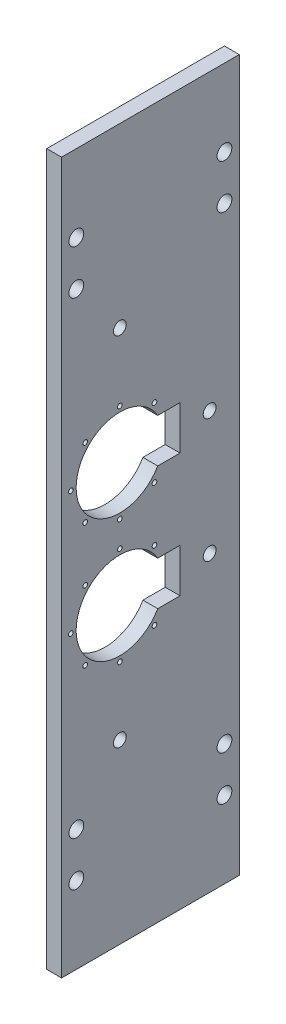
SolidWorks part; units mm, degrees
material "1060 Alloy"
ref_plane "Front Plane" through (0, 0, 0) normal (1, 0, 0) x (0, 1, 0)
ref_plane "Top Plane" through (0, 0, 0) normal (0, 0, 1) x (0, 1, 0)
ref_plane "Right Plane" through (0, 0, 0) normal (0, 1, 0) x (-1, 0, 0)
sketch "Sketch1" plane through (0, 0, 0) normal (1, 0, 0) x (0, 1, 0)
  line L0 (0, 76.2) -> (0, -76.2) construction
  line L1 (-304.8, 76.2) -> (304.8, 76.2)
  line L2 (-304.8, 76.2) -> (-304.8, -76.2)
  line L3 (-304.8, -76.2) -> (304.8, -76.2)
  line L4 (304.8, 76.2) -> (304.8, -76.2)
  line L5 (-304.8, 76.2) -> (304.8, -76.2) construction
  line L6 (-304.8, -76.2) -> (304.8, 76.2) construction
  line L7 (53, 26.2) -> (53, -11.3) construction
  line L8 (53, 26.2) -> (71.75, -6.276) construction
  line L9 (34.25, -6.276) -> (34.25, -25.4)
  line L10 (34.25, -25.4) -> (71.75, -25.4)
  line L11 (71.75, -25.4) -> (71.75, -6.276)
  line L12 (-304.8, 0) -> (304.8, 0) construction
  line L13 (-34.25, -25.4) -> (-71.75, -25.4)
  line L14 (-34.25, -6.276) -> (-34.25, -25.4)
  line L15 (-71.75, -25.4) -> (-71.75, -6.276)
  arc A0 (71.75, -6.276) -> (34.25, -6.276) centre (53, 26.2) ccw
  circle A1 centre (53, 26.2) radius 42 construction
  circle A2 centre (53, 68.2) radius 2
  circle A3 centre (82.6985, 55.8985) radius 2
  circle A4 centre (95, 26.2) radius 2
  circle A5 centre (82.6985, -3.4985) radius 2
  circle A6 centre (53, -15.8) radius 2 [skipped]
  circle A7 centre (23.3015, -3.4985) radius 2
  circle A8 centre (11, 26.2) radius 2
  circle A9 centre (23.3015, 55.8985) radius 2
  circle A10 centre (238.76, 63.5) radius 6.35
  circle A11 centre (200.66, 63.5) radius 6.35
  circle A12 centre (200.66, -63.5) radius 6.35
  circle A13 centre (238.76, -63.5) radius 6.35
  circle A14 centre (-200.66, 63.5) radius 6.35
  circle A15 centre (-238.76, 63.5) radius 6.35
  circle A16 centre (-238.76, -63.5) radius 6.35
  circle A17 centre (-200.66, -63.5) radius 6.35
  circle A18 centre (-82.6985, -3.4985) radius 2
  circle A19 centre (-95, 26.2) radius 2
  circle A20 centre (-82.6985, 55.8985) radius 2
  circle A21 centre (-53, 68.2) radius 2
  circle A22 centre (-23.3015, 55.8985) radius 2
  circle A23 centre (-11, 26.2) radius 2
  circle A24 centre (-23.3015, -3.4985) radius 2
  arc A25 (-71.75, -6.276) -> (-34.25, -6.276) centre (-53, 26.2) cw
  point P0 (0, 0)
  point P8 (53, 26.2)
  point P18 (53, -50.8)
  point P19 (153, 26.2)
  point P71 (-153, 26.2)
  point P72 (-53, -50.8)
  dimension "D9" = 84
  dimension "D10" = 4
  dimension "D14" = 12.7
  dimension "D17" = 12.7
  dimension "D1" = 152.4
  dimension "D2" = 609.6
  dimension "D3" = 50
  dimension "D4" = 53
  dimension "D5" = 37.5
  dimension "D6" = 30
  dimension "D7" = 60
  dimension "D8" = 50.8
  dimension "D12" = 25.4
  dimension "D13" = 100
  dimension "D15" = 12.7
  dimension "D16" = 66.04
  dimension "D18" = 12.7
  dimension "D19" = 38.1
  dimension "D22" = 53
  dimension "D23" = 50
  dimension "D11" = 8
extrude "Boss-Extrude1" add sketch "Sketch1" along normal mid plane 12.7
hole_wizard "M12x1.0 Tapped Hole1" positions "Sketch2" profile "Sketch3" tap size "M12x1.0" standard "ISO" end condition through all
sketch "Sketch2" plane through (6.35, 0, 0) normal (1, 0, 0) x (0, 0, -1)
  point P0 (50.8, 53)
  point P3 (-26.2, 153)
  point P6 (50.8, -53)
  point P9 (-26.2, -153)
sketch "Sketch3" plane through (6.35, 53, -50.8) normal (0, 1, 0) x (0, 0, -1)
  line L0 (0, 0) -> (0, 12.7)
  line L1 (0, 12.7) -> (5.5, 12.7)
  line L2 (5.5, 12.7) -> (5.5, 0)
  line L5 (5.5, 0) -> (0, 0)
  line L11 (0, -6.35) -> (0, 107.95) construction
  dimension "Thru Tap Drill Dia." = 11
  dimension "Thru Tap Drill Depth" = 12.7
